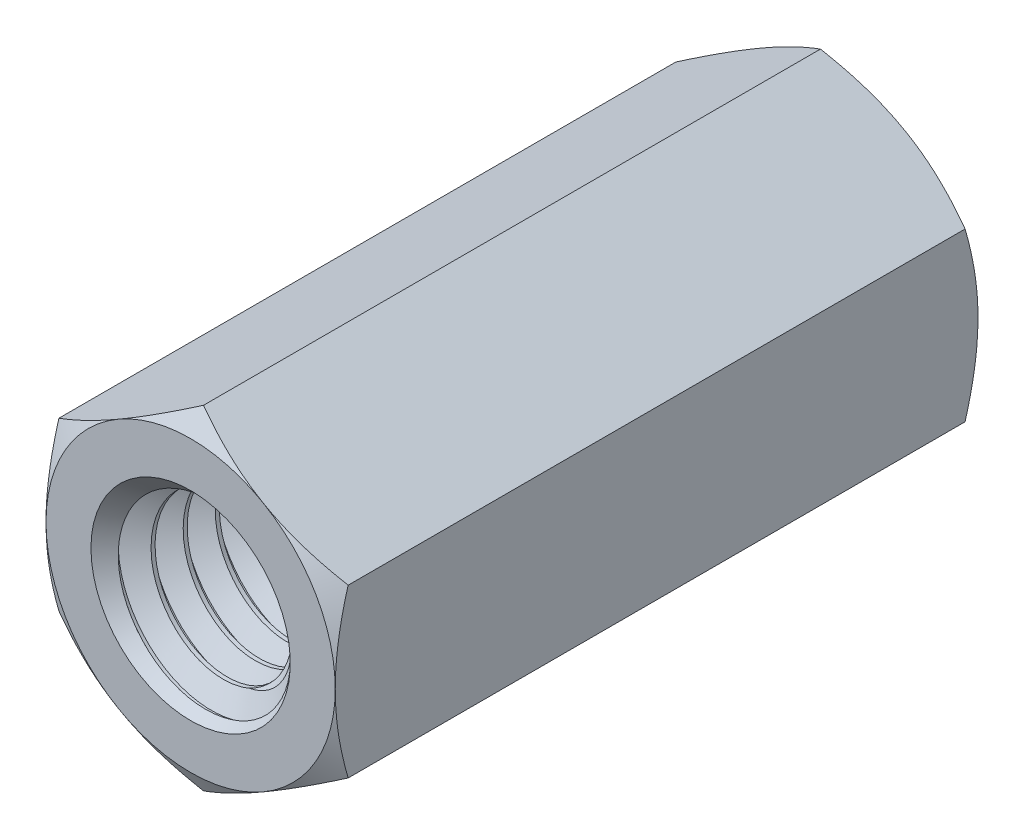
SolidWorks part; units mm, degrees
ref_plane "Front Plane" through (0, 0, 0) normal (0, 0, 1) x (1, 0, 0)
ref_plane "Top Plane" through (0, 0, 0) normal (0, 1, 0) x (1, 0, 0)
ref_plane "Right Plane" through (0, 0, 0) normal (1, 0, 0) x (0, 0, -1)
sketch "Sketch3" plane through (0, 0, 0) normal (1, 0, 0) x (0, 0, -1)
  line L0 (-5, 0) -> (5, 0) construction
  line L1 (0, 2.25) -> (0, -2.25) construction
  line L2 (-5, 1.5) -> (-5, -1.5) construction
  point P2 (0.2, 0)
  point P3 (-0.2, 0)
  dimension "D1" = 4.8
  dimension "Length" = 10
  dimension "Min Thread Length" = 4.8
  dimension "Thread Dia" = 3
  dimension "Hex" = 4.5
sketch "Sketch1" plane through (0, 0, 0) normal (0, 0, 1) x (1, 0, 0)
  line L1 (0, 2.5981) -> (-2.25, 1.299)
  line L2 (-2.25, 1.299) -> (-2.25, -1.299)
  line L3 (-2.25, -1.299) -> (0, -2.5981)
  line L4 (0, -2.5981) -> (2.25, -1.299)
  line L5 (2.25, -1.299) -> (2.25, 1.299)
  line L6 (2.25, 1.299) -> (0, 2.5981)
  circle A0 centre (0, 0) radius 2.25 construction
  circle A1 centre (0, 0) radius 1.5
extrude "Extrude1" add sketch "Sketch1" along normal up to vertex (5 mm away) and the other way up to vertex (5 mm away) up to point (0, 0, 5) other way up to point (0, 0, -5)
sketch "Sketch11" plane through (0, 0, -5) normal (0, 0, -1) x (-1, 0, 0)
  circle A0 centre (0, 0) radius 1.5 construction
  circle A1 centre (0, 0) radius 1.5
curve "Helix/Spiral1" pitch 0.5 height 10.5 radius 1.5 centre (0, 0, -5) axis (0, 0, 1) start towards (0, 1, 0) parameters "Pitch"=0.5
sketch "Sketch12" plane through (0, 0, 0) normal (1, 0, 0) x (0, 0, -1)
  line L0 (5.4375, 1.5) -> (5, 1.5)
  line L1 (5.4375, 1.5) -> (5.25, 1.1752)
  line L2 (5.25, 1.1752) -> (5.1875, 1.1752)
  line L3 (5.1875, 1.1752) -> (5, 1.5)
  line L4 (5.2188, 1.1752) -> (5.2188, 1.5) construction
  line L5 (5.3438, 1.3376) -> (5.0938, 1.3376) construction
  dimension "D1" = 0.0625
  dimension "D2" = 0.25
  dimension "D3" = 60
sweep "Sweep1" add profiles "Sketch12" path "Helix/Spiral1"
sketch "Sketch6" plane through (0, 0, -5) normal (0, 0, -1) x (-1, 0, 0)
  line L6 (0, 2.5981) -> (-2.25, 1.299)
  line L7 (-2.25, 1.299) -> (-2.25, -1.299)
  line L8 (-2.25, -1.299) -> (0, -2.5981)
  line L9 (0, -2.5981) -> (2.25, -1.299)
  line L10 (2.25, -1.299) -> (2.25, 1.299)
  line L11 (2.25, 1.299) -> (0, 2.5981)
  line L12 (0, 2.5981) -> (-2.25, 1.299)
  line L13 (-2.25, 1.299) -> (-2.25, -1.299)
  line L14 (-2.25, -1.299) -> (0, -2.5981)
  line L15 (0, -2.5981) -> (2.25, -1.299)
  line L16 (2.25, -1.299) -> (2.25, 1.299)
  line L17 (2.25, 1.299) -> (0, 2.5981)
  dimension "D1" = 0
extrude "Extrude2" cut sketch "Sketch6" along normal through all
sketch "Sketch7" plane through (0, 0, -5) normal (0, 0, -1) x (-1, 0, 0)
  circle A2 centre (0, 0) radius 1.5508
  circle A3 centre (0, 0) radius 1.5508
  dimension "D1" = 0.0508
extrude "Extrude3" cut sketch "Sketch7" against normal through all draft 43
sketch "Sketch8" plane through (0, 0, -5) normal (0, 0, -1) x (-1, 0, 0)
  circle A0 centre (0, 0) radius 2.25 construction
  circle A1 centre (0, 0) radius 2.25
extrude "Extrude4" cut sketch "Sketch8" against normal through all draft 60 flip side to cut
mirror "Mirror1" about plane through (0, 0, 0) normal (0, 0, 1) of "Extrude2", "Extrude3", "Extrude4"
sketch "Sketch9" [suppressed] plane through (0, 0, 0) normal (1, 0, 0) x (0, 0, -1)
  line L1 (-1.2, 1.1353) -> (1.2, 1.1353)
  line L2 (-1.2, 1.1353) -> (-1.2, 0)
  line L3 (-1.2, 0) -> (1.2, 0)
  line L4 (1.2, 1.1353) -> (1.2, 0)
  line L7 (-6, 0) -> (6, 0) construction
revolve "Revolve" [suppressed] add sketch "Sketch9" angle 360 about L0
sketch "Sketch10" [suppressed] plane through (0, 0, 0) normal (1, 0, 0) x (0, 0, -1)
  line L0 (6, 1.25) -> (1.2, 1.25)
  line L1 (-6, 1.25) -> (-1.2, 1.25)
  line L2 (1.2, 1.25) -> (1.2, -1.25)
  line L3 (-6, -1.25) -> (-1.2, -1.25)
  line L4 (-1.2, 1.25) -> (-1.2, -1.25)
  line L5 (1.2, -1.25) -> (6, -1.25)
equation "\"D1@Sketch3\" = \"Min Thread Length@Sketch3\""
equation "\"D3@Helix/Spiral1\" = \"Length@Sketch3\"+\"Pitch@Helix/Spiral1\""
equation "\"D1@Sketch12\" = \"Pitch@Helix/Spiral1\"*.125"
equation "\"D2@Sketch12\" = \"Pitch@Helix/Spiral1\"*.5"
